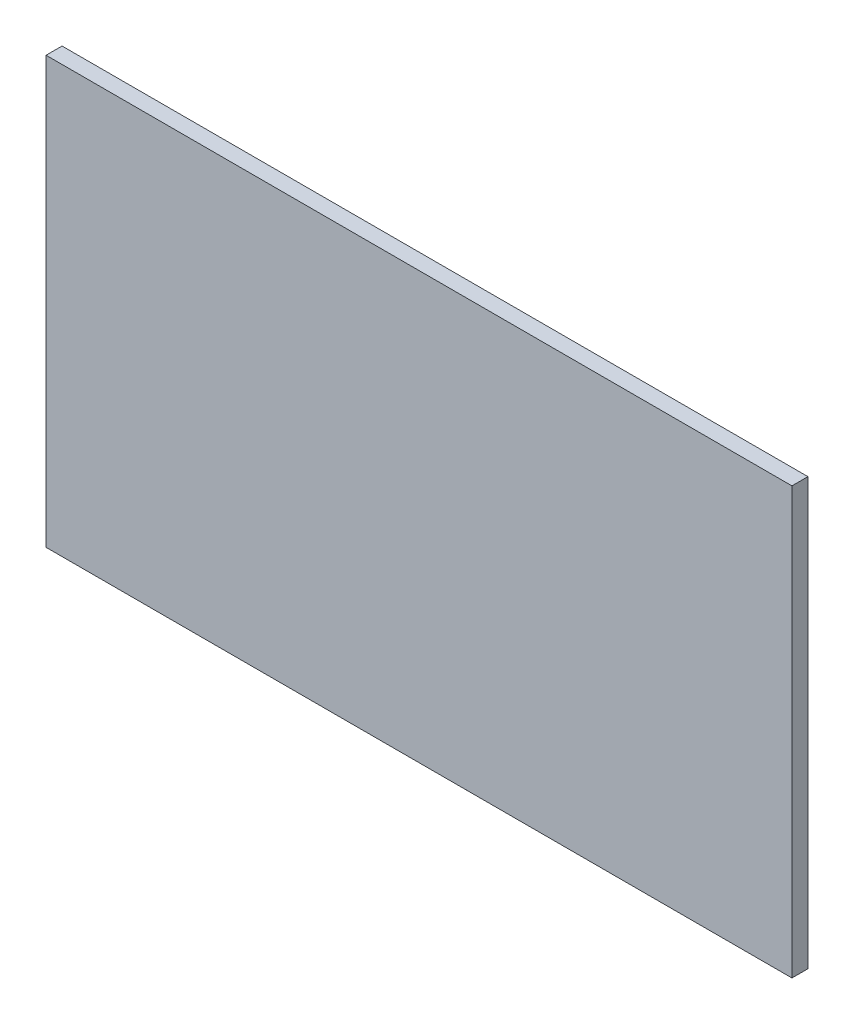
SolidWorks part; units mm, degrees
ref_plane "前视基准面" through (0, 0, 0) normal (0, 0, 1) x (1, 0, 0)
ref_plane "上视基准面" through (0, 0, 0) normal (0, 1, 0) x (1, 0, 0)
ref_plane "右视基准面" through (0, 0, 0) normal (1, 0, 0) x (0, 0, -1)
sketch "草图1" plane through (0, 0, 0) normal (0, 0, 1) x (1, 0, 0)
  line L0 (-35, -20) -> (35, -20)
  line L1 (35, -20) -> (35, 20)
  line L2 (35, 20) -> (-35, 20)
  line L3 (-35, 20) -> (-35, -20)
base flange "基体-法兰1" sketch "草图1" thickness 1.5 reverse thickness direction no parameters "D1"=1.5
sketch "折弯-线1" [suppressed] plane through (0, 0, 0) normal (0, 1, 0) x (1, 0, 0)
sketch "边界框1" [suppressed] plane through (0, 0, 0) normal (0, 1, 0) x (1, 0, 0)
sheet metal parameters "钣金2" thickness 1.5 parameters "D1"=1.5
flat pattern "平板型式2" [suppressed]
sketch "折弯-线2" plane through (0, 0, 0) normal (0, 1, 0) x (1, 0, 0)
sketch3d "边界框2" [suppressed]
  line L0 (35, -20, 0) -> (-35, -20, 0) construction
  line L1 (35, 20, 0) -> (-35, 20, 0) construction
  line L2 (35, -20, 0) -> (35, 20, 0) construction
  line L3 (-35, -20, 0) -> (-35, 20, 0) construction
